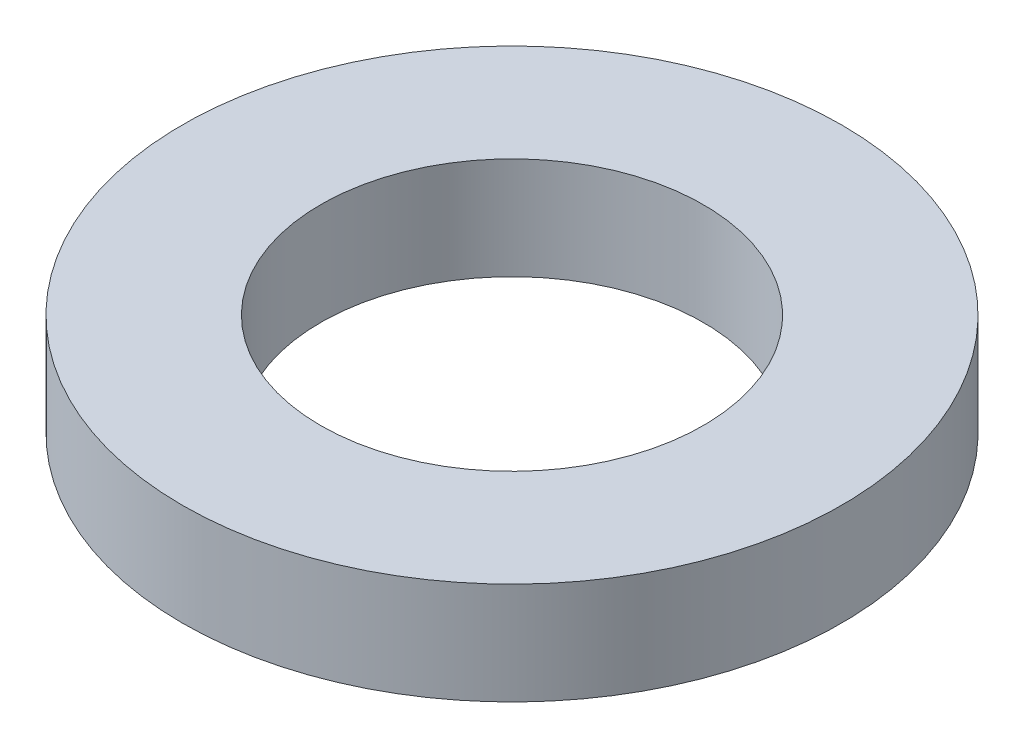
SolidWorks part; units mm, degrees
ref_plane "Front Plane" through (0, 0, 0) normal (0, 0, 1) x (1, 0, 0)
ref_plane "Top Plane" through (0, 0, 0) normal (0, 1, 0) x (1, 0, 0)
ref_plane "Right Plane" through (0, 0, 0) normal (1, 0, 0) x (0, 0, -1)
sketch "Sketch1" plane through (0, 0, 0) normal (0, 1, 0) x (1, 0, 0)
  circle A0 centre (0, 0) radius 77.5
  dimension "FLANGE_OD" = 155
extrude "Boss-Extrude1" add sketch "Sketch1" along normal blind 24
sketch "Sketch2" plane through (0, 0, 0) normal (0, 1, 0) x (1, 0, 0)
  circle A0 centre (0, 0) radius 45
  dimension "BORE_D" = 90
extrude "Cut-Extrude1" cut sketch "Sketch2" along normal through all
sketch "Sketch3" plane through (0, 24, 0) normal (0, 1, 0) x (1, 0, 0)
  circle A0 centre (0, 0) radius 31.2563 construction
  circle A1 centre (-31.2563, 0) radius 4.7156
  dimension "BOLT_D" = 9.4312
  dimension "BOLT_PCD" = 62.5126
extrude "Cut-Extrude2" cut sketch "Sketch3" against normal blind 15.7698 rebuild error yes
pattern_circular "CirPattern1" count 5 over 360 rebuild error yes
